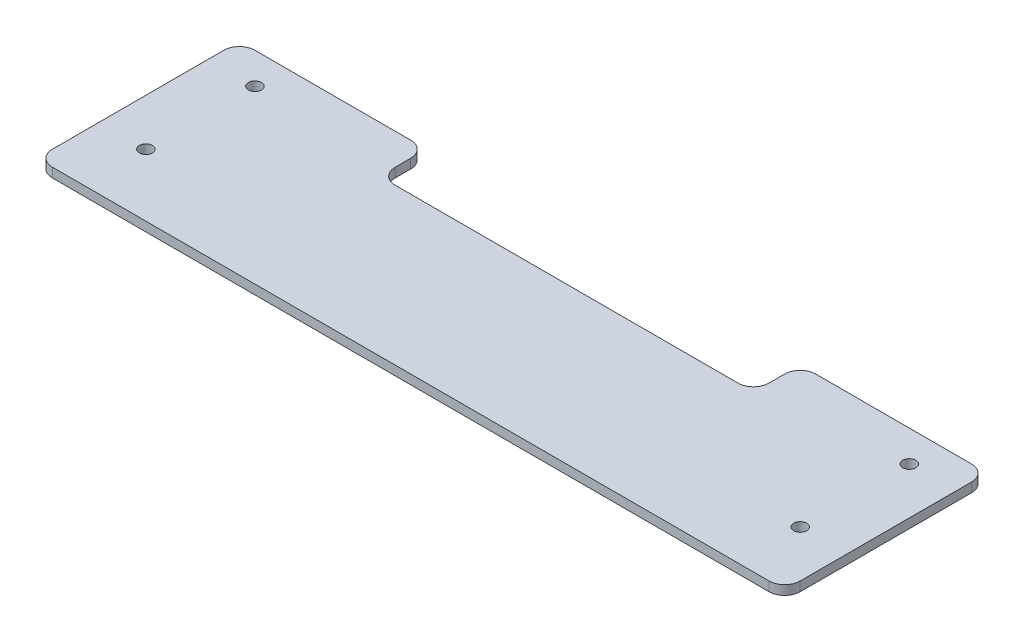
SolidWorks part; units mm, degrees
material "Thornel Mat VMA"
ref_plane "前视基准面" through (0, 0, 0) normal (0, 0, 1) x (1, 0, 0)
ref_plane "上视基准面" through (0, 0, 0) normal (0, 1, 0) x (1, 0, 0)
ref_plane "右视基准面" through (0, 0, 0) normal (1, 0, 0) x (0, 0, -1)
sketch "草图1" plane through (0, 0, 0) normal (0, 1, 0) x (1, 0, 0)
  line L0 (-105, 57.5) -> (-105, -7.5) construction
  line L1 (-120, -7.5) -> (120, -7.5)
  line L2 (-120, -7.5) -> (-120, 57.5)
  line L3 (-120, 57.5) -> (120, 57.5)
  line L4 (120, -7.5) -> (120, 57.5)
  line L5 (-120, -7.5) -> (120, 57.5) construction
  line L6 (-120, 57.5) -> (120, -7.5) construction
  line L7 (0, 57.5) -> (0, -7.5) construction
  line L8 (0, -57.5) -> (0, -7.5) construction
  line L9 (-60, -7.5) -> (20, -7.5)
  circle A0 centre (-105, 47.5) radius 2.1
  circle A1 centre (-105, 12.5) radius 2.1
  circle A2 centre (105, 12.5) radius 2.1
  circle A3 centre (105, 47.5) radius 2.1
  point P0 (0, 25)
  dimension "D1" = 65
  dimension "D2" = 240
  dimension "D3" = 15
  dimension "D4" = 35
  dimension "D5" = 20
extrude "凸台-拉伸1" add sketch "草图1" along normal blind 3 contours L1 L4 L3 L2 A2 A1 A0 A3 region at (0, 0, -24.9822)
sketch "草图2" plane through (0, 3, 0) normal (0, 1, 0) x (1, 0, 0)
  line L0 (0, 57.5) -> (0, -7.5) construction
  line L1 (-120, 57.5) -> (120, 57.5) construction
  line L2 (-120, -7.5) -> (120, -7.5) construction
  line L3 (-60, 57.5) -> (-60, 42.5)
  line L4 (-60, 42.5) -> (60, 42.5)
  line L5 (60, 57.5) -> (60, 42.5)
  line L6 (-60, 57.5) -> (60, 57.5)
  point P10 (0, 42.5)
  dimension "D1" = 15
  dimension "D2" = 60
extrude "切除-拉伸1" cut sketch "草图2" against normal blind 3
fillet "圆角1" radius 5 8 edges at (120, 1.5, 7.5) (-120, 1.5, 7.5) (-120, 1.5, -57.5) (120, 1.5, -57.5) (60, 1.5, -57.5) (60, 1.5, -42.5) (-60, 1.5, -42.5) (-60, 1.5, -57.5)
